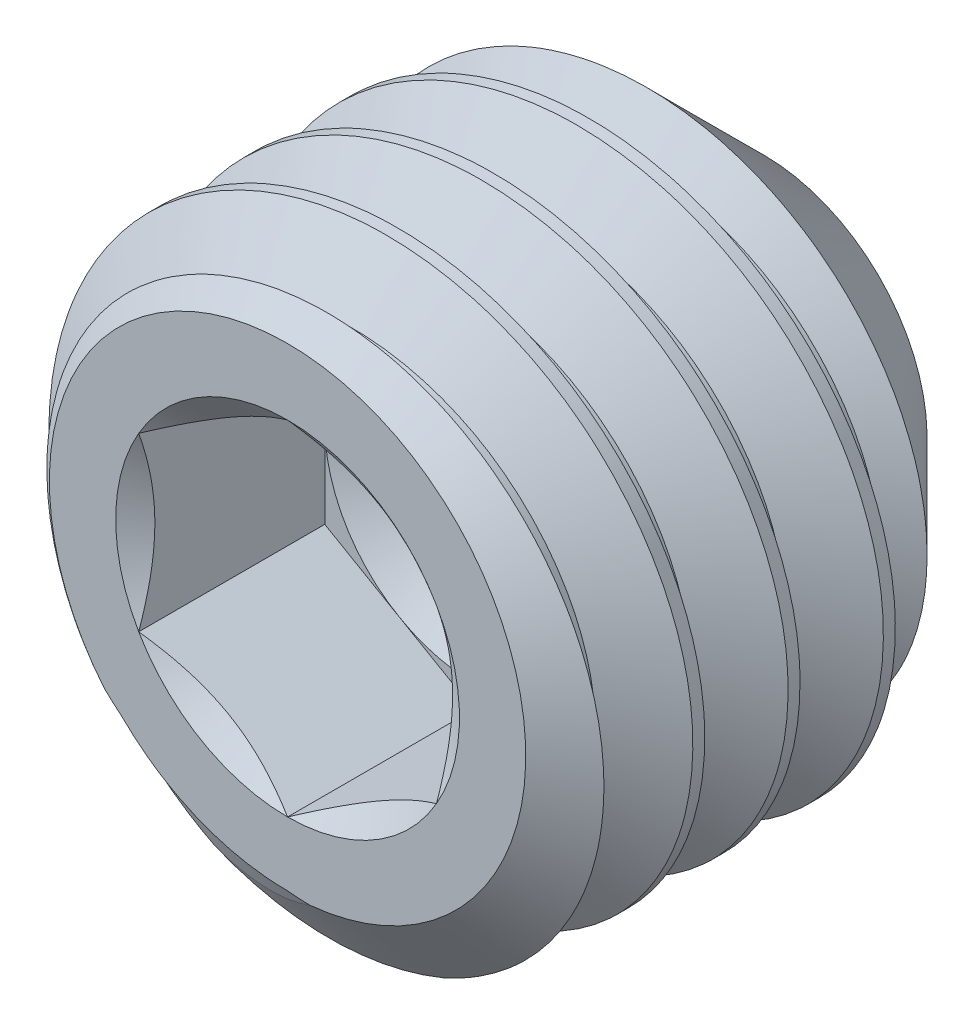
SolidWorks part; units mm, degrees
ref_plane "Front" through (0, 0, 0) normal (0, 0, 1) x (1, 0, 0)
ref_plane "Top" through (0, 0, 0) normal (0, 1, 0) x (1, 0, 0)
ref_plane "Right" through (0, 0, 0) normal (1, 0, 0) x (0, 0, -1)
sketch "Body Sketch" plane through (0, 0, 0) normal (1, 0, 0) x (0, 0, -1)
  line L0 (-1.5884, 0) -> (-1.5884, 2)
  line L1 (-1.5884, 2) -> (-1.2383, 2.5)
  line L2 (-1.2383, 2.5) -> (1.2815, 2.5)
  line L3 (1.2815, 2.5) -> (2.4116, 1.3699)
  line L4 (0.0216, 2.5) -> (0.0216, -2.5) construction
  line L5 (1.5884, 0) -> (-1.5884, 0)
  line L6 (-1.5884, 2) -> (-1.5884, -2) construction
  line L7 (1.5884, 0) -> (2.4116, 1.3699)
  line L8 (1.5884, 0) -> (2.4116, -1.3699) construction
  line L10 (1.5884, 0) -> (2.4116, 0) construction
  line L11 (2.4116, 1.3699) -> (2.4116, 0) construction
  point P11 (0.0216, 0)
  dimension "Length" = 4
  dimension "Top Chamfer" = 35
  dimension "Diameter" = 5
  dimension "D1" = 4
  dimension "D2" = 118
  dimension "D3" = 45
revolve "Body Revolve" add sketch "Body Sketch" angle 360 about L5
ref_plane "Bottom of Tip Plane" through (0, 0, -2.4116) normal (0, 0, 1) x (1, 0, 0)
sketch "Spiral Sketch" plane through (0, 0, -2.4116) normal (0, 0, 1) x (1, 0, 0)
  circle A0 centre (0, 0) radius 2.5 construction
  circle A1 centre (0, 0) radius 2.5
curve "Helix/Spiral" pitch 0.8 height 4.8 radius 2.5 centre (0, 0, -2.4116) axis (0, 0, 1) start towards (0, 1, 0) parameters "Thread Pitch"=0.8
sketch "Cut Sweep Sketch" plane through (0, 0, 0) normal (1, 0, 0) x (0, 0, -1)
  line L0 (2.4116, 2.5) -> (3.1116, 2.5)
  line L1 (3.1116, 2.5) -> (2.8116, 1.9804)
  line L2 (2.8116, 1.9804) -> (2.7116, 1.9804)
  line L3 (2.7116, 1.9804) -> (2.4116, 2.5)
  line L4 (2.5616, 2.2402) -> (2.9616, 2.2402) construction
  line L6 (-1.2383, 2.5) -> (1.2815, 2.5) construction
  dimension "D1" = 0.1
  dimension "D3" = 60
  dimension "D2" = 0.4
sweep "Cut Sweep" cut profiles "Cut Sweep Sketch" path "Helix/Spiral" align with end faces yes
sketch "Hex Sketch" plane through (0, 0, 1.5884) normal (0, 0, 1) x (1, 0, 0)
  line L1 (0, 1.4434) -> (-1.25, 0.7217)
  line L2 (-1.25, 0.7217) -> (-1.25, -0.7217)
  line L3 (-1.25, -0.7217) -> (0, -1.4434)
  line L4 (0, -1.4434) -> (1.25, -0.7217)
  line L5 (1.25, -0.7217) -> (1.25, 0.7217)
  line L6 (1.25, 0.7217) -> (0, 1.4434)
  circle A0 centre (0, 0) radius 1.25 construction
  dimension "Hex" = 2.5
extrude "Hex Extrude" cut sketch "Hex Sketch" against normal blind 1.5625
sketch "Hex Entry Sketch" plane through (0, 0, 1.5884) normal (0, 0, 1) x (1, 0, 0)
  circle A0 centre (0, 0) radius 1.4434
extrude "Hex Entry Extrude" cut sketch "Hex Entry Sketch" against normal through all draft 55
sketch "Hex Bottom Sketch" plane through (0, 0, 0.0259) normal (0, 0, 1) x (1, 0, 0)
  circle A0 centre (0, 0) radius 1.25 construction
  circle A1 centre (0, 0) radius 1.25
extrude "Hex Bottom Extrude" cut sketch "Hex Bottom Sketch" against normal through all draft 60
equation "\"D1@Cut Sweep Sketch\" = \"Thread Pitch@Helix/Spiral\" * .125"
equation "\"D2@Cut Sweep Sketch\" = \"Thread Pitch@Helix/Spiral\" * .5"
equation "\"D3@Helix/Spiral\" = \"Length@Body Sketch\" + \"Thread Pitch@Helix/Spiral\""
equation "\"hex Depth@Hex Extrude\" = \"Hex@Hex Sketch\" * .625"
equation "\"D1@Body Sketch\" = \"Diameter@Body Sketch\" * .8"
equation "\"Diameter\"= 5mm"
equation "\"Thread Pitch\"= 0.8mm"
equation "\"Hex Size\"= 2.5mm"
equation "\"Diameter@Body Sketch\"=\"Diameter\""
equation "\"Thread Pitch@Helix/Spiral\"=\"Thread Pitch\""
equation "\"Hex@Hex Sketch\"=\"Hex Size\""
